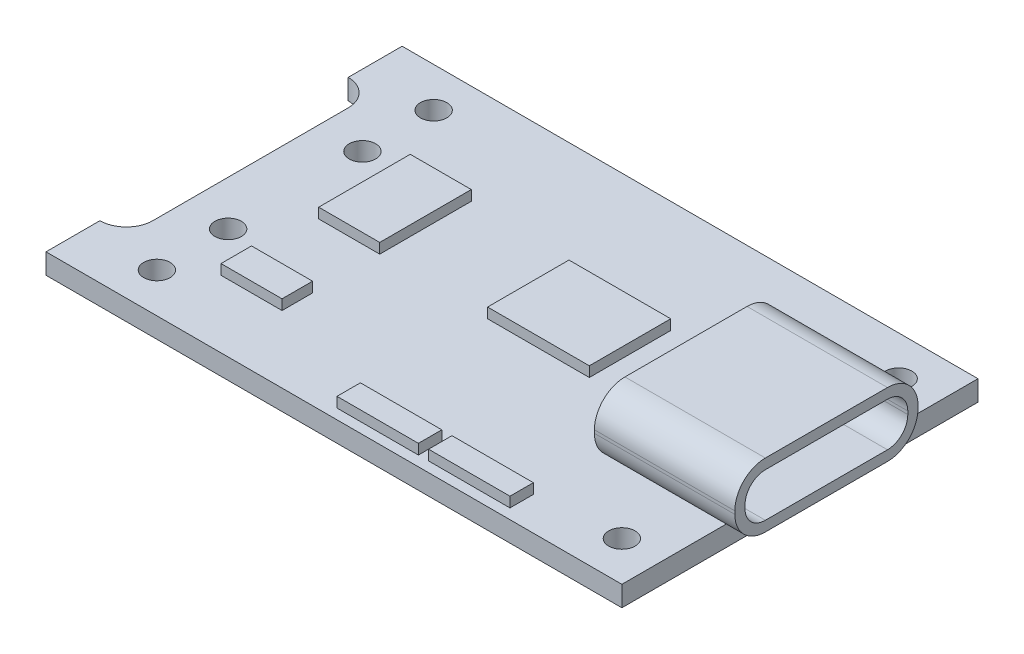
SolidWorks part; units mm, degrees
ref_plane "Alzado" through (0, 0, 0) normal (0, 0, 1) x (1, 0, 0)
ref_plane "Planta" through (0, 0, 0) normal (0, 1, 0) x (1, 0, 0)
ref_plane "Vista lateral" through (0, 0, 0) normal (1, 0, 0) x (0, 0, -1)
sketch "Croquis1" plane through (0, 0, 0) normal (0, 1, 0) x (1, 0, 0)
  line L0 (16.4731, 0) -> (-16.4731, 0) construction
  line L1 (-14.15, 8.75) -> (14.15, 8.75)
  line L2 (-14.15, 8.75) -> (-14.15, -8.75) construction
  line L3 (-14.15, -8.75) -> (14.15, -8.75)
  line L4 (14.15, 8.75) -> (14.15, -8.75)
  line L5 (-14.15, 8.75) -> (14.15, -8.75) construction
  line L6 (-14.15, -8.75) -> (14.15, 8.75) construction
  line L7 (-12.85, 4.8) -> (-12.85, -4.8)
  line L8 (-14.15, 8.75) -> (-14.15, 6.1)
  line L9 (-14.15, -8.75) -> (-14.15, -6.1)
  arc A0 (-14.15, 6.1) -> (-12.85, 4.8) centre (-14.15, 4.8) cw
  arc A1 (-14.15, -6.1) -> (-12.85, -4.8) centre (-14.15, -4.8) ccw
  circle A2 centre (12.2, 6.8) radius 0.65
  circle A3 centre (12.2, -6.8) radius 0.65
  circle A4 centre (-10.65, 6.8) radius 0.65
  circle A5 centre (-10.65, 3.3) radius 0.65
  circle A6 centre (-10.65, -3.3) radius 0.65
  circle A7 centre (-10.65, -6.8) radius 0.65
  point P0 (0, 0)
  point P9 (0, 0)
  point P13 (-12.85, 0)
  point P18 (12.85, 6.8)
  point P20 (12.2, 7.45)
  dimension "D6" = 1.3
  dimension "D1" = 28.3
  dimension "D2" = 17.5
  dimension "D3" = 2.65
  dimension "D4" = 1.3
  dimension "D5" = 1.3
  dimension "D7" = 1.3
  dimension "D8" = 3.5
  dimension "D9" = 3.5
extrude "Saliente-Extruir1" add sketch "Croquis1" along normal blind 1
sketch "Croquis2" plane through (0, 1, 0) normal (0, 1, 0) x (1, 0, 0)
  line L0 (14.15, -8.75) -> (14.15, 8.75) construction
  line L1 (8.55, 4.5) -> (15.45, 4.5)
  line L2 (8.55, 4.5) -> (8.55, -4.5)
  line L3 (8.55, -4.5) -> (15.45, -4.5)
  line L4 (15.45, 4.5) -> (15.45, -4.5)
  point P4 (8.55, 0)
  dimension "D1" = 6.9
  dimension "D2" = 9
  dimension "D3" = 1.3
extrude "Saliente-Extruir2" add sketch "Croquis2" along normal blind 3.15 separate body
fillet "Redondeo1" radius 1.5 4 edges at (12, 1, -4.5) (12, 1, 4.5) (12, 4.15, 4.5) (12, 4.15, -4.5)
shell "Vaciado1" thickness 0.5 removed face at (15.45, 2.575, 0)
sketch "Croquis3" plane through (0, 1, 0) normal (0, 1, 0) x (1, 0, 0)
  line L0 (14.15, -8.75) -> (14.15, 8.75) construction
  line L1 (-0.35, -7.1) -> (3.65, -7.1)
  line L2 (-0.35, -7.1) -> (-0.35, -8.25)
  line L3 (-0.35, -8.25) -> (3.65, -8.25)
  line L4 (3.65, -7.1) -> (3.65, -8.25)
  line L5 (4.15, -7.1) -> (8.15, -7.1)
  line L6 (4.15, -7.1) -> (4.15, -8.25)
  line L7 (4.15, -8.25) -> (8.15, -8.25)
  line L8 (8.15, -7.1) -> (8.15, -8.25)
  line L9 (-14.15, -8.75) -> (14.15, -8.75) construction
  dimension "D1" = 1.15
  dimension "D2" = 4
  dimension "D3" = 6
  dimension "D4" = 0.5
  dimension "D5" = 0.5
extrude "Saliente-Extruir3" add sketch "Croquis3" along normal blind 0.5 separate body
sketch "Croquis4" plane through (0, 1, 0) normal (0, 1, 0) x (1, 0, 0)
  line L0 (8.55, 3) -> (8.55, -3) construction
  line L1 (-8.85, -3.95) -> (-5.85, -3.95)
  line L2 (-8.85, -3.95) -> (-8.85, -5.45)
  line L3 (-8.85, -5.45) -> (-5.85, -5.45)
  line L4 (-5.85, -3.95) -> (-5.85, -5.45)
  line L5 (-8.85, 3.85) -> (-5.85, 3.85)
  line L6 (-8.85, 3.85) -> (-8.85, -0.65)
  line L7 (-8.85, -0.65) -> (-5.85, -0.65)
  line L8 (-5.85, 3.85) -> (-5.85, -0.65)
  line L9 (-0.45, 3.25) -> (4.55, 3.25)
  line L10 (-0.45, 3.25) -> (-0.45, -0.75)
  line L11 (-0.45, -0.75) -> (4.55, -0.75)
  line L12 (4.55, 3.25) -> (4.55, -0.75)
  line L13 (14.15, 8.75) -> (-14.15, 8.75) construction
  line L14 (-14.15, -8.75) -> (14.15, -8.75) construction
  line L15 (-12.85, 4.8) -> (-12.85, -4.8) construction
  dimension "D1" = 4
  dimension "D2" = 5.5
  dimension "D3" = 5
  dimension "D4" = 4
  dimension "D5" = 1.5
  dimension "D6" = 3
  dimension "D7" = 4.5
  dimension "D8" = 3.3
  dimension "D9" = 3.3
  dimension "D10" = 4
extrude "Saliente-Extruir4" add sketch "Croquis4" along normal blind 0.5 separate body
